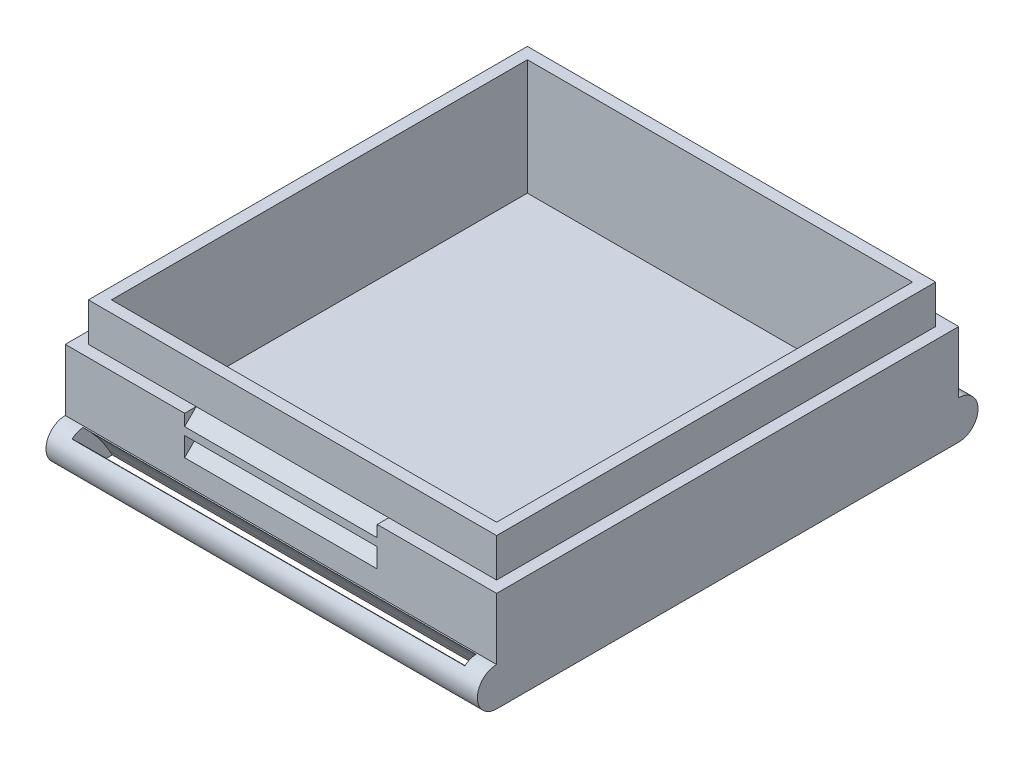
SolidWorks part; units mm, degrees
ref_plane "Front Plane" through (0, 0, 0) normal (0, 0, 1) x (1, 0, 0)
ref_plane "Top Plane" through (0, 0, 0) normal (0, 1, 0) x (1, 0, 0)
ref_plane "Right Plane" through (0, 0, 0) normal (1, 0, 0) x (0, 0, -1)
sketch "Sketch1" plane through (0, 0, 0) normal (0, 1, 0) x (1, 0, 0)
  line L0 (-28, 30) -> (28, 30)
  line L1 (-25, -27) -> (25, -27)
  line L2 (-25, -27) -> (-25, 27)
  line L3 (-25, 27) -> (25, 27)
  line L4 (25, -27) -> (25, 27)
  line L5 (-25, -27) -> (25, 27) construction
  line L6 (-25, 27) -> (25, -27) construction
  line L7 (28, -30) -> (28, 30)
  line L8 (-28, -30) -> (28, -30)
  line L9 (-28, -30) -> (-28, 30)
  point P0 (0, 0)
  dimension "D1" = 50
  dimension "D2" = 54
  dimension "D3" = 3
extrude "Boss-Extrude1" add sketch "Sketch1" along normal blind 10
sketch "Sketch2" plane through (0, 0, 0) normal (0, -1, 0) x (1, 0, 0)
  line L4 (-28, 30) -> (-28, -30)
  line L5 (-28, -30) -> (28, -30)
  line L6 (28, -30) -> (28, 30)
  line L7 (28, 30) -> (-28, 30)
  line L8 (-28, 30) -> (-28, -30)
  line L9 (-28, -30) -> (28, -30)
  line L10 (28, -30) -> (28, 30)
  line L11 (28, 30) -> (-28, 30)
  dimension "D1" = 0
extrude "Boss-Extrude2" add sketch "Sketch2" along normal blind 3
sketch "Sketch3" plane through (0, 0, 0) normal (1, 0, 0) x (0, 0, -1)
  line L0 (-28.5, 10) -> (-31, 10)
  line L1 (-31, 10) -> (-31, 4)
  line L3 (-28.5, 7.5) -> (-30, 7.5)
  line L4 (-30, 7.5) -> (-30, 8.5)
  line L5 (-30, 8.5) -> (-28.5, 10)
  line L6 (-28.5, 7.5) -> (-28.5, 6.5)
  line L7 (-28.5, 6.5) -> (-31, 4)
  line L8 (-30, 10) -> (-30, -3) construction
  line L9 (30, 10) -> (-30, 10) construction
  dimension "D1" = 1.5
  dimension "D2" = 45
  dimension "D3" = 1
  dimension "D4" = 1
  dimension "D5" = 1
extrude "Cut-Extrude1" cut sketch "Sketch3" against normal mid plane 25
mirror "Mirror1" about plane through (0, 0, 0) normal (0, 0, 1) of "Cut-Extrude1"
sketch "Sketch4" plane through (0, 0, 0) normal (1, 0, 0) x (0, 0, -1)
  line L0 (30, 8.5) -> (30, 10) construction
  line L1 (30, 2) -> (30, -3)
  arc A0 (30, 2) -> (30, -3) centre (30, -0.5) cw
  dimension "D1" = 5
extrude "Boss-Extrude4" add sketch "Sketch4" along normal up to surface and the other way up to surface up to face at (28, 3.5, 0) other way up to face at (-28, 3.5, 0)
sketch "Sketch5" plane through (0, 0, 0) normal (1, 0, 0) x (0, 0, -1)
  line L0 (30, -3) -> (-30, -3) construction
  line L1 (26.7876, -2.3) -> (26.3834, -3)
  line L2 (26.3834, -3) -> (28, -3)
  line L3 (32.5, 2.1264) -> (32.5, 3.8529)
  line L8 (-27, 0) -> (27, 0)
  line L9 (27, 0) -> (27, 10)
  line L10 (27, 10) -> (-27, 10)
  line L11 (-27, 10) -> (-27, 0)
  line L12 (-27, 0) -> (27, 0) construction
  line L13 (27, 0) -> (27, 10) construction
  line L14 (27, 10) -> (-27, 10) construction
  line L15 (-27, 10) -> (-27, 0) construction
  arc A0 (32.5, 2.1264) -> (28, -3) centre (43.104, -11.7203) ccw
  arc A2 (32.5, 3.8529) -> (26.7876, -2.3) centre (43.104, -11.7203) ccw
  arc A3 (33.288, 2.6957) -> (28, -3) centre (43.104, -11.7203) ccw construction
  arc A4 (30, -3) -> (30, 2) centre (30, -0.5) ccw construction
  dimension "D3" = 2
  dimension "D4" = 60
  dimension "D1" = 1.4
  dimension "D2" = 0
extrude "Boss-Extrude5" add sketch "Sketch5" along normal mid plane 51 separate body
sketch "Sketch6" plane through (0, 0, 0) normal (1, 0, 0) x (0, 0, -1)
  line L0 (26.3834, -3) -> (28, -3) construction
  line L1 (26.7876, -2.3) -> (26.3834, -3) construction
  line L2 (32.5, 2.1264) -> (32.5, 3.8529) construction
  line L3 (26.3834, -3) -> (28, -3)
  line L4 (26.7876, -2.3) -> (26.3834, -3)
  line L5 (32.5, 2.1264) -> (32.5, 3.8529)
  arc A0 (32.5, 2.1264) -> (28, -3) centre (43.104, -11.7203) ccw construction
  arc A1 (32.5, 3.8529) -> (26.7876, -2.3) centre (43.104, -11.7203) ccw construction
  arc A2 (32.5, 2.1264) -> (28, -3) centre (43.104, -11.7203) ccw
  arc A3 (32.5, 3.8529) -> (26.7876, -2.3) centre (43.104, -11.7203) ccw
mirror "Mirror2" about plane through (0, 0, 0) normal (0, 0, 1) of bodies 107 108 109
mirror "Mirror3" about plane through (0, 0, 0) normal (0, 0, 1) of "Boss-Extrude4"
sketch "Sketch7" plane through (0, 10, 0) normal (0, 1, 0) x (1, 0, 0)
  line L0 (-12.5, 30) -> (-28, 30) construction
  line L1 (26.5, -28.5) -> (-26.5, -28.5)
  line L2 (26.5, -28.5) -> (26.5, 28.5)
  line L3 (26.5, 28.5) -> (-26.5, 28.5)
  line L4 (-26.5, -28.5) -> (-26.5, 28.5)
  line L5 (26.5, -28.5) -> (-26.5, 28.5) construction
  line L6 (26.5, 28.5) -> (-26.5, -28.5) construction
  line L7 (-28, 30) -> (-28, -30) construction
  line L9 (25, -27) -> (-25, -27)
  line L10 (25, -27) -> (25, 27)
  line L11 (25, 27) -> (-25, 27)
  line L12 (-25, -27) -> (-25, 27)
  line L13 (25, -27) -> (-25, 27) construction
  line L14 (25, 27) -> (-25, -27) construction
  point P0 (0, 0)
  point P10 (0, 0)
  dimension "D1" = 1.5
  dimension "D2" = 1.5
extrude "Boss-Extrude6" add sketch "Sketch7" along normal blind 5
combine bodies "Combine1" operation type subtract main body 114 bodies to subtract 107 115
